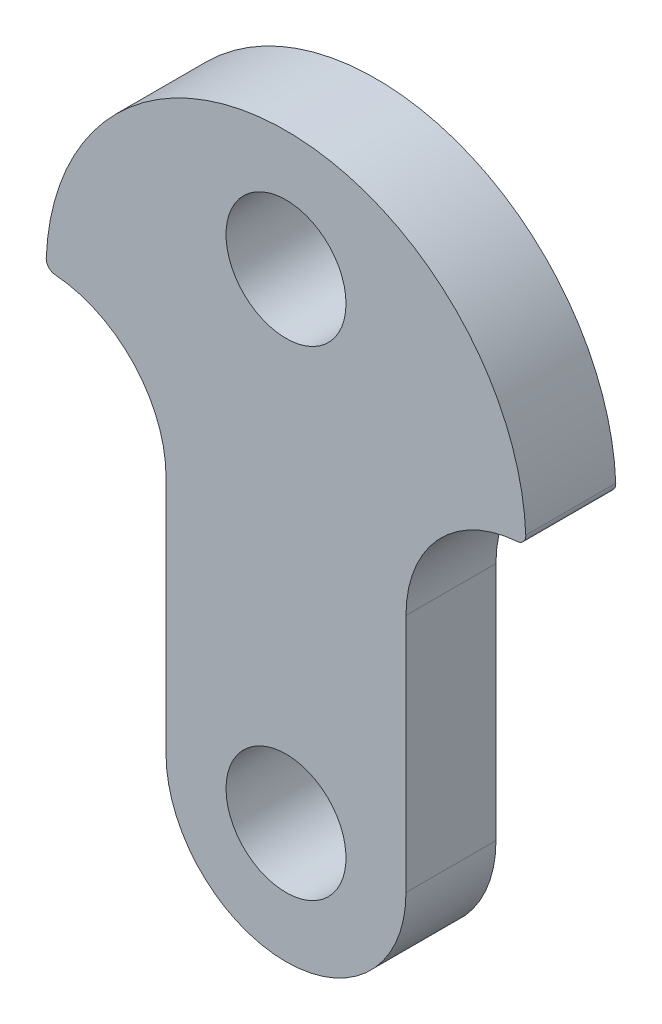
SolidWorks part; units mm, degrees
ref_plane "Front Plane" through (0, 0, 0) normal (0, 0, 1) x (1, 0, 0)
ref_plane "Top Plane" through (0, 0, 0) normal (0, 1, 0) x (1, 0, 0)
ref_plane "Right Plane" through (0, 0, 0) normal (1, 0, 0) x (0, 0, -1)
sketch "Sketch1" plane through (0, 0, 0) normal (0, 0, 1) x (1, 0, 0)
  line L0 (0, 0) -> (12.7, 0)
  line L1 (12.7, 0) -> (12.7, -38.1)
  line L3 (38.1, -38.1) -> (38.1, 0)
  line L4 (38.1, 0) -> (50.8, 0)
  arc A0 (38.1, -38.1) -> (12.7, -38.1) centre (25.4, -38.1) cw
  arc A1 (50.8, 0) -> (0, 0) centre (25.4, 0) ccw
  circle A2 centre (25.4, -38.1) radius 6.35
  point P9 (-55.1174, 2.6834)
  point P10 (-55.1174, 5.3492)
  point P12 (0, 0)
  point P13 (-50.8851, 2.4407)
  dimension "D1" = 25.4
  dimension "D2" = 12.7
  dimension "D3" = 12.7
  dimension "D4" = 38.1
extrude "Boss-Extrude1" add sketch "Sketch1" along normal blind 9.525
sketch "Sketch2" plane through (0, 0, 9.525) normal (0, 0, 1) x (1, 0, 0)
  circle A0 centre (25.4, 12.7) radius 6.35
  arc A1 (50.8, 0) -> (0, 0) centre (25.4, 0) ccw construction
  point P5 (25.4, 25.4)
  dimension "D1" = 12.7
  dimension "D2" = 0
  dimension "D3" = 12.7
extrude "Cut-Extrude1" cut sketch "Sketch2" against normal through all
fillet "Fillet1" radius 12.7 2 edges at (38.1, 0, 4.7625) (12.7, 0, 4.7625)
fillet "Fillet2" radius 1 2 edges at (50.8, 0, 4.7625) (0, 0, 4.7625)
